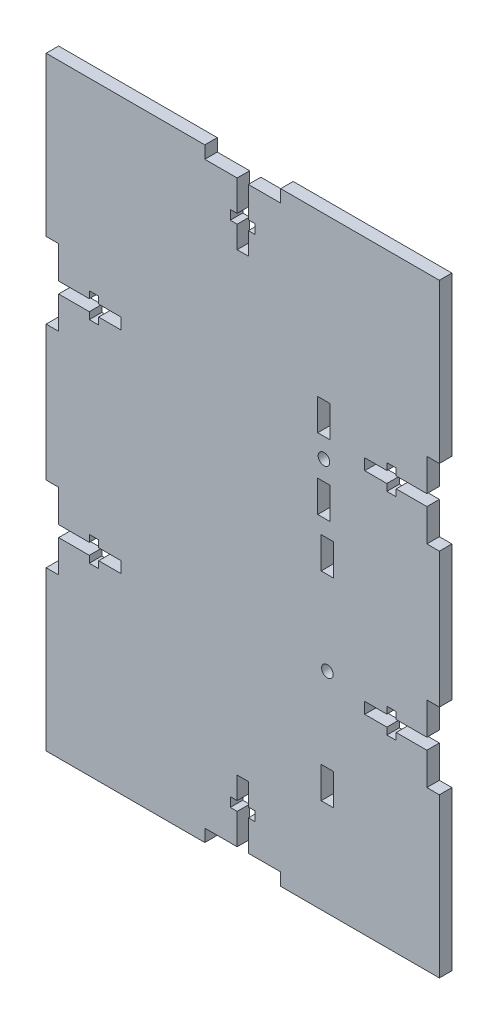
SolidWorks part; units mm, degrees
ref_plane "Front Plane" through (0, 0, 0) normal (0, 0, 1) x (1, 0, 0)
ref_plane "Top Plane" through (0, 0, 0) normal (0, 1, 0) x (1, 0, 0)
ref_plane "Right Plane" through (0, 0, 0) normal (1, 0, 0) x (0, 0, -1)
sketch "Sketch1" plane through (0, 0, 0) normal (0, 0, 1) x (1, 0, 0)
  line L0 (-50, 76.825) -> (-16.6667, 76.825)
  line L1 (-50, -76.825) -> (50, -76.825)
  line L2 (-50, -76.825) -> (-50, 76.825)
  line L3 (-50, 76.825) -> (50, 76.825) construction
  line L4 (50, -76.825) -> (50, 76.825)
  line L5 (-50, -76.825) -> (50, 76.825) construction
  line L6 (-50, 76.825) -> (50, -76.825) construction
  line L7 (-16.6667, 76.825) -> (16.6667, 76.825)
  line L8 (16.6667, 76.825) -> (50, 76.825)
  point P0 (0, 0)
  dimension "D1" = 100
  dimension "D2" = 153.65
extrude "Boss-Extrude1" add sketch "Sketch1" along normal blind 3.18
sketch "Sketch3" [suppressed] plane through (0, 0, 0) normal (0, 0, -1) x (-1, 0, 0)
  line L0 (-32.675, 34.075) -> (-32.675, -61.675)
  line L1 (-32.675, -61.675) -> (32.675, -61.675)
  line L2 (32.675, -61.675) -> (32.675, 34.075)
  line L3 (32.675, 34.075) -> (9.5, 34.075)
  line L4 (9.5, 34.075) -> (9.5, 37.075)
  line L5 (9.5, 37.075) -> (-9.5, 37.075)
  line L6 (-9.5, 37.075) -> (-9.5, 34.075)
  line L7 (-9.5, 34.075) -> (-32.675, 34.075)
  line L8 (32.675, 44.075) -> (-32.675, 44.075)
  line L9 (32.675, -61.675) -> (32.675, 44.075)
  line L10 (-32.675, -61.675) -> (32.675, -61.675)
  line L11 (-32.675, 44.075) -> (-32.675, -61.675)
  line L12 (-32.675, -61.675) -> (-32.675, -73.645) construction
  line L13 (44.645, -73.645) -> (-44.645, -73.645) construction
  line L14 (-32.675, -61.675) -> (-44.645, -61.675) construction
  line L15 (-44.645, -73.645) -> (-44.645, 73.645) construction
  line L16 (32.675, -61.675) -> (44.645, -61.675) construction
  line L17 (44.645, 73.645) -> (44.645, -73.645) construction
  dimension "D1" = 65.35
  dimension "D2" = 95.75
  dimension "D3" = 105.75
  dimension "D4" = 19
  dimension "D5" = 3
extrude "Cut-Extrude1" [suppressed] cut sketch "Sketch3" against normal through all contours L6 L7 L0 L1 L2 L3 L4 L5
sketch "Sketch9" [suppressed] plane through (-44.645, 0, 0) normal (-1, 0, 0) x (0, 0, 1)
  line L0 (0, 0) -> (3.18, 0) construction
  line L1 (0, 50) -> (0, -50) construction
  line L2 (3.18, 50) -> (3.18, -50) construction
  line L4 (0, -9.65) -> (3.18, -9.65)
  line L5 (0, -9.65) -> (0, 9.65)
  line L6 (0, 9.65) -> (3.18, 9.65)
  line L7 (3.18, -9.65) -> (3.18, 9.65)
  line L8 (0, -9.65) -> (3.18, 9.65) construction
  line L9 (0, 9.65) -> (3.18, -9.65) construction
  point P6 (1.59, 0)
  dimension "D1" = 19.3
extrude "Boss-Extrude4" [suppressed] add sketch "Sketch9" along normal blind 3.18
sketch "Sketch10" [suppressed] plane through (0, 0, 3.18) normal (0, 0, 1) x (1, 0, 0)
  line L0 (-46.235, 9.65) -> (-46.235, -9.65) construction
  line L1 (-47.825, 9.65) -> (-44.645, 9.65) construction
  line L2 (-47.825, -9.65) -> (-44.645, -9.65) construction
  circle A0 centre (-46.235, 0) radius 1.425
extrude "Cut-Extrude4" [suppressed] cut sketch "Sketch10" against normal through all
mirror "Mirror1" [suppressed] about plane through (0, 0, 0) normal (1, 0, 0)
sketch "Sketch18" [suppressed] plane through (44.645, 0, 0) normal (1, 0, 0) x (0, 0, -1)
  line L0 (0, 0) -> (-3.18, 0) construction
  line L1 (0, -50) -> (0, 50) construction
  line L2 (-3.18, -50) -> (-3.18, 50) construction
  line L4 (-3.18, -9.65) -> (0, -9.65)
  line L5 (-3.18, -9.65) -> (-3.18, 9.65)
  line L6 (-3.18, 9.65) -> (0, 9.65)
  line L7 (0, -9.65) -> (0, 9.65)
  line L8 (-3.18, -9.65) -> (0, 9.65) construction
  line L9 (-3.18, 9.65) -> (0, -9.65) construction
  point P6 (-1.59, 0)
  dimension "D1" = 19.3
extrude "Boss-Extrude8" [suppressed] add sketch "Sketch18" along normal blind 3.18
sketch "Sketch19" [suppressed] plane through (0, 0, 3.18) normal (0, 0, 1) x (1, 0, 0)
  line L0 (46.235, -9.65) -> (46.235, 9.65) construction
  line L1 (47.825, -9.65) -> (44.645, -9.65) construction
  line L2 (47.825, 9.65) -> (44.645, 9.65) construction
  circle A0 centre (46.235, 0) radius 1.425
extrude "Cut-Extrude8" [suppressed] cut sketch "Sketch19" against normal through all
mirror "Mirror2" [suppressed] about plane through (0, 0, 0) normal (1, 0, 0)
sketch "Sketch20" plane through (0, 0, 3.18) normal (0, 0, 1) x (1, 0, 0)
  line L0 (0, 70.465) -> (0, 0) construction
  line L1 (50, 76.825) -> (-50, 76.825) construction
  line L2 (-9.65, 76.825) -> (9.65, 76.825)
  line L3 (9.65, 76.825) -> (9.65, 73.645)
  line L4 (9.65, 73.645) -> (1.425, 73.645)
  line L5 (1.425, 73.645) -> (1.425, 65.845)
  line L6 (1.425, 65.845) -> (3.175, 65.845)
  line L7 (3.175, 65.845) -> (3.175, 63.465)
  line L8 (3.175, 63.465) -> (1.425, 63.465)
  line L9 (1.425, 63.465) -> (1.425, 57.845)
  line L10 (1.425, 57.845) -> (-1.425, 57.845)
  line L11 (-1.425, 57.845) -> (-1.425, 63.465)
  line L12 (-1.425, 63.465) -> (-3.175, 63.465)
  line L13 (-3.175, 63.465) -> (-3.175, 65.845)
  line L14 (-3.175, 65.845) -> (-1.425, 65.845)
  line L15 (-1.425, 65.845) -> (-1.425, 73.645)
  line L16 (-1.425, 73.645) -> (-9.65, 73.645)
  line L17 (-9.65, 73.645) -> (-9.65, 76.825)
  dimension "D1" = 19.3
  dimension "D2" = 3.18
  dimension "D3" = 15.8
  dimension "D4" = 6.35
  dimension "D5" = 2.38
  dimension "D6" = 2.85
  dimension "D7" = 7.8
extrude "Cut-Extrude9" cut sketch "Sketch20" against normal through all
mirror "Mirror3" about plane through (0, 0, 0) normal (0, 1, 0) of "Cut-Extrude9"
sketch "Sketch23" plane through (0, 0, 3.18) normal (0, 0, 1) x (1, 0, 0)
  line L0 (-50, 17.175) -> (-50, 36.475)
  line L1 (-50, 76.825) -> (-50, -76.825) construction
  line L2 (-50, 36.475) -> (-46.82, 36.475)
  line L3 (-46.82, 36.475) -> (-46.82, 28.25)
  line L4 (-46.82, 28.25) -> (-39.02, 28.25)
  line L5 (-39.02, 28.25) -> (-39.02, 30)
  line L6 (-39.02, 30) -> (-36.64, 30)
  line L7 (-36.64, 30) -> (-36.64, 28.25)
  line L8 (-36.64, 28.25) -> (-31.02, 28.25)
  line L9 (-31.02, 28.25) -> (-31.02, 25.4)
  line L10 (-31.02, 25.4) -> (-36.64, 25.4)
  line L11 (-36.64, 25.4) -> (-36.64, 23.65)
  line L12 (-36.64, 23.65) -> (-39.02, 23.65)
  line L13 (-39.02, 23.65) -> (-39.02, 25.4)
  line L14 (-39.02, 25.4) -> (-46.82, 25.4)
  line L15 (-46.82, 25.4) -> (-46.82, 17.175)
  line L16 (-46.82, 17.175) -> (-50, 17.175)
  line L17 (-9.65, 76.825) -> (-50, 76.825) construction
  line L19 (-31.02, 26.825) -> (-50, 26.825) construction
  line L20 (-50, -36.475) -> (-50, -17.175)
  line L21 (-50, -17.175) -> (-46.82, -17.175)
  line L22 (-46.82, -17.175) -> (-46.82, -25.4)
  line L23 (-46.82, -25.4) -> (-39.02, -25.4)
  line L24 (-39.02, -25.4) -> (-39.02, -23.65)
  line L25 (-39.02, -23.65) -> (-36.64, -23.65)
  line L26 (-36.64, -23.65) -> (-36.64, -25.4)
  line L27 (-36.64, -25.4) -> (-31.02, -25.4)
  line L28 (-31.02, -25.4) -> (-31.02, -28.25)
  line L29 (-31.02, -28.25) -> (-36.64, -28.25)
  line L30 (-36.64, -28.25) -> (-36.64, -30)
  line L31 (-36.64, -30) -> (-39.02, -30)
  line L32 (-39.02, -30) -> (-39.02, -28.25)
  line L33 (-39.02, -28.25) -> (-46.82, -28.25)
  line L34 (-46.82, -28.25) -> (-46.82, -36.475)
  line L35 (-46.82, -36.475) -> (-50, -36.475)
  line L36 (-50, -26.825) -> (-31.02, -26.825) construction
  line L37 (-50, -76.825) -> (-9.65, -76.825) construction
  dimension "D1" = 50
  dimension "D2" = 19.3
  dimension "D3" = 3.18
  dimension "D4" = 15.8
  dimension "D5" = 6.35
  dimension "D6" = 2.85
  dimension "D7" = 7.8
  dimension "D8" = 2.38
  dimension "D9" = 19.3
  dimension "D10" = 3.18
  dimension "D11" = 7.8
  dimension "D12" = 15.8
  dimension "D13" = 6.35
  dimension "D14" = 2.85
  dimension "D15" = 2.38
  dimension "D16" = 50
  dimension "D17" = 1.75
extrude "Cut-Extrude10" cut sketch "Sketch23" against normal through all
sketch "Sketch24" [suppressed] plane through (0, 0, 3.18) normal (0, 0, 1) x (1, 0, 0)
  line L0 (50, -17.175) -> (50, -36.475)
  line L1 (50, -76.825) -> (50, 76.825) construction
  line L2 (50, -36.475) -> (46.82, -36.475)
  line L3 (46.82, -36.475) -> (46.82, -28.25)
  line L4 (46.82, -28.25) -> (39.02, -28.25)
  line L5 (39.02, -28.25) -> (39.02, -30)
  line L6 (39.02, -30) -> (36.64, -30)
  line L7 (36.64, -30) -> (36.64, -28.25)
  line L8 (36.64, -28.25) -> (31.02, -28.25)
  line L9 (31.02, -28.25) -> (31.02, -25.4)
  line L10 (31.02, -25.4) -> (36.64, -25.4)
  line L11 (36.64, -25.4) -> (36.64, -23.65)
  line L12 (36.64, -23.65) -> (39.02, -23.65)
  line L13 (39.02, -23.65) -> (39.02, -25.4)
  line L14 (39.02, -25.4) -> (46.82, -25.4)
  line L15 (46.82, -25.4) -> (46.82, -17.175)
  line L16 (46.82, -17.175) -> (50, -17.175)
  line L17 (31.02, -26.825) -> (50, -26.825) construction
  line L18 (9.65, -76.825) -> (50, -76.825) construction
  line L19 (50, 36.475) -> (50, 17.175)
  line L20 (50, 17.175) -> (46.82, 17.175)
  line L21 (46.82, 17.175) -> (46.82, 25.4)
  line L22 (46.82, 25.4) -> (39.02, 25.4)
  line L23 (39.02, 25.4) -> (39.02, 23.65)
  line L24 (39.02, 23.65) -> (36.64, 23.65)
  line L25 (36.64, 23.65) -> (36.64, 25.4)
  line L26 (36.64, 25.4) -> (31.02, 25.4)
  line L27 (31.02, 25.4) -> (31.02, 28.25)
  line L28 (31.02, 28.25) -> (36.64, 28.25)
  line L29 (36.64, 28.25) -> (36.64, 30)
  line L30 (36.64, 30) -> (39.02, 30)
  line L31 (39.02, 30) -> (39.02, 28.25)
  line L32 (39.02, 28.25) -> (46.82, 28.25)
  line L33 (46.82, 28.25) -> (46.82, 36.475)
  line L34 (46.82, 36.475) -> (50, 36.475)
  line L35 (31.02, 26.825) -> (50, 26.825) construction
  line L36 (50, 76.825) -> (9.65, 76.825) construction
  dimension "D1" = 19.3
  dimension "D2" = 3.18
  dimension "D3" = 15.8
  dimension "D4" = 7.8
  dimension "D5" = 6.35
  dimension "D6" = 2.85
  dimension "D7" = 2.38
  dimension "D8" = 50
  dimension "D9" = 19.3
  dimension "D10" = 3.18
  dimension "D11" = 7.8
  dimension "D12" = 15.8
  dimension "D13" = 6.35
  dimension "D14" = 2.85
  dimension "D15" = 2.38
  dimension "D16" = 50
extrude "Cut-Extrude11" [suppressed] cut sketch "Sketch24" against normal through all
sketch "Sketch25" [suppressed] plane through (0, 0, 3.18) normal (0, 0, 1) x (1, 0, 0)
  line L0 (9.65, -50) -> (-9.65, -50)
  line L1 (-44.645, -50) -> (44.645, -50) construction
  line L2 (-9.65, -50) -> (-9.65, -46.82)
  line L3 (-9.65, -46.82) -> (-1.425, -46.82)
  line L4 (-1.425, -46.82) -> (-1.425, -39.02)
  line L5 (-1.425, -39.02) -> (-3.175, -39.02)
  line L6 (-3.175, -39.02) -> (-3.175, -36.64)
  line L7 (-3.175, -36.64) -> (-1.425, -36.64)
  line L8 (-1.425, -36.64) -> (-1.425, -31.02)
  line L9 (-1.425, -31.02) -> (1.425, -31.02)
  line L10 (1.425, -31.02) -> (1.425, -36.64)
  line L11 (1.425, -36.64) -> (3.175, -36.64)
  line L12 (3.175, -36.64) -> (3.175, -39.02)
  line L13 (3.175, -39.02) -> (1.425, -39.02)
  line L14 (1.425, -39.02) -> (1.425, -46.82)
  line L15 (1.425, -46.82) -> (9.65, -46.82)
  line L16 (9.65, -46.82) -> (9.65, -50)
  line L17 (0, -50) -> (0, 0) construction
  dimension "D1" = 19.3
  dimension "D2" = 3.18
  dimension "D3" = 15.8
  dimension "D4" = 7.8
  dimension "D5" = 6.35
  dimension "D6" = 2.85
  dimension "D7" = 2.38
extrude "Cut-Extrude12" [suppressed] cut sketch "Sketch25" against normal through all
sketch "Sketch26" [suppressed] plane through (0, 0, 3.18) normal (0, 0, 1) x (1, 0, 0)
  line L0 (-9.65, 50) -> (9.65, 50)
  line L1 (44.645, 50) -> (-44.645, 50) construction
  line L2 (9.65, 50) -> (9.65, 46.82)
  line L3 (9.65, 46.82) -> (1.425, 46.82)
  line L4 (1.425, 46.82) -> (1.425, 39.02)
  line L5 (1.425, 39.02) -> (3.175, 39.02)
  line L6 (3.175, 39.02) -> (3.175, 36.64)
  line L7 (3.175, 36.64) -> (1.425, 36.64)
  line L8 (1.425, 36.64) -> (1.425, 31.02)
  line L9 (1.425, 31.02) -> (-1.425, 31.02)
  line L10 (-1.425, 31.02) -> (-1.425, 36.64)
  line L11 (-1.425, 36.64) -> (-3.175, 36.64)
  line L12 (-3.175, 36.64) -> (-3.175, 39.02)
  line L13 (-3.175, 39.02) -> (-1.425, 39.02)
  line L14 (-1.425, 39.02) -> (-1.425, 46.82)
  line L15 (-1.425, 46.82) -> (-9.65, 46.82)
  line L16 (-9.65, 46.82) -> (-9.65, 50)
  line L17 (0, 50) -> (0, -4.4192) construction
  dimension "D1" = 19.3
  dimension "D2" = 3.18
  dimension "D3" = 7.8
  dimension "D4" = 15.8
  dimension "D5" = 6.35
  dimension "D6" = 2.85
  dimension "D7" = 2.38
extrude "Cut-Extrude13" [suppressed] cut sketch "Sketch26" against normal through all
mirror "Mirror4" about plane through (0, 0, 0) normal (1, 0, 0) of "Cut-Extrude10"
mirror "Mirror5" [suppressed] about plane through (0, 0, 0) normal (1, 0, 0)
mirror "Mirror6" [suppressed] about plane through (0, 0, 0) normal (0, 1, 0)
mirror "Mirror7" [suppressed] about plane through (0, 0, 0) normal (0, 1, 0)
sketch "Sketch27" [suppressed] plane through (-44.645, 0, 0) normal (-1, 0, 0) x (0, 0, 1)
  line L0 (0, -36.475) -> (0, -17.175)
  line L1 (0, 73.645) -> (0, -73.645) construction
  line L2 (0, -17.175) -> (3.18, -17.175)
  line L3 (3.18, 73.645) -> (3.18, -73.645) construction
  line L4 (3.18, -17.175) -> (3.18, -36.475)
  line L5 (3.18, -36.475) -> (0, -36.475)
  line L6 (3.18, -26.825) -> (0, -26.825) construction
  line L7 (3.18, -73.645) -> (0, -73.645) construction
  dimension "D1" = 19.3
  dimension "D2" = 46.82
extrude "Boss-Extrude9" [suppressed] add sketch "Sketch27" along normal blind 3.18
sketch "Sketch28" [suppressed] plane through (0, -73.645, 0) normal (0, -1, 0) x (1, 0, 0)
  line L0 (9.65, 0) -> (-9.65, 0)
  line L1 (-44.645, 0) -> (44.645, 0) construction
  line L2 (-9.65, 0) -> (-9.65, 3.18)
  line L3 (-44.645, 3.18) -> (44.645, 3.18) construction
  line L4 (-9.65, 3.18) -> (9.65, 3.18)
  line L5 (9.65, 3.18) -> (9.65, 0)
  line L6 (0, 0) -> (0, 3.18) construction
  dimension "D1" = 19.3
extrude "Boss-Extrude10" [suppressed] add sketch "Sketch28" along normal blind 3.18
sketch "Sketch29" [suppressed] plane through (0, 0, 3.18) normal (0, 0, 1) x (1, 0, 0)
  line L0 (-47.825, -26.825) -> (-37.3062, -26.825) construction
  line L1 (-47.825, -36.475) -> (-47.825, -17.175) construction
  line L2 (-46.235, -17.175) -> (-46.235, -36.475) construction
  line L3 (-47.825, -17.175) -> (-44.645, -17.175) construction
  line L4 (-47.825, -36.475) -> (-44.645, -36.475) construction
  circle A0 centre (-46.235, -26.825) radius 1.425
extrude "Cut-Extrude14" [suppressed] cut sketch "Sketch29" against normal through all
sketch "Sketch30" [suppressed] plane through (0, 0, 3.18) normal (0, 0, 1) x (1, 0, 0)
  line L0 (0, -76.825) -> (0, -66.2855) construction
  line L1 (9.65, -76.825) -> (-9.65, -76.825) construction
  line L2 (9.65, -75.235) -> (-9.65, -75.235) construction
  line L3 (9.65, -76.825) -> (9.65, -73.645) construction
  line L4 (-9.65, -76.825) -> (-9.65, -73.645) construction
  circle A0 centre (0, -75.235) radius 1.425
extrude "Cut-Extrude15" [suppressed] cut sketch "Sketch30" against normal through all
mirror "Mirror8" [suppressed] about plane through (0, 0, 0) normal (1, 0, 0)
mirror "Mirror9" [suppressed] about plane through (0, 0, 0) normal (0, 1, 0)
sketch "Sketch31" [suppressed] plane through (0, 0, 3.18) normal (0, 0, 1) x (1, 0, 0)
  line L0 (14.341, -8.1358) -> (14.341, -12.6358) construction
  line L8 (5.175, -1.9558) -> (5.175, 19.3642) construction
  line L10 (-24.825, 19.3642) -> (-24.825, -1.9558) construction
  line L11 (5.175, 19.3642) -> (-24.825, 19.3642) construction
  line L16 (23.507, -9.6358) -> (39.341, -9.6358) construction
  line L17 (23.507, 19.3642) -> (23.507, -9.6358) construction
  line L18 (39.341, 19.3642) -> (23.507, 19.3642) construction
  line L19 (39.341, -9.6358) -> (39.341, 19.3642) construction
  line L26 (14.341, -15.8158) -> (14.341, -12.6358) construction
  line L29 (-24.825, -1.9558) -> (5.175, -1.9558) construction
  line L34 (20.5772, -7.1358) -> (20.5772, 11.3642) construction
  line L35 (20.5772, 11.3642) -> (8.1048, 11.3642) construction
  line L36 (8.1048, 11.3642) -> (8.1048, -7.1358) construction
  line L37 (9.7431, -8.1358) -> (18.9389, -8.1358) construction
  line L38 (14.341, -15.8158) -> (14.341, -50) construction
  line L39 (-17.325, 9.65) -> (-24.825, 9.65) construction
  line L40 (-6.159, -12.4758) -> (34.841, -12.4758)
  line L41 (-6.159, -12.4758) -> (-6.159, -15.9758)
  line L42 (-6.159, -15.9758) -> (34.841, -15.9758)
  line L43 (34.841, -12.4758) -> (34.841, -15.9758)
  line L88 (-44.645, -50) -> (-9.65, -50) construction
  line L89 (-9.65, -50) -> (-9.65, -46.82) construction
  line L90 (-9.65, -46.82) -> (-1.425, -46.82) construction
  line L91 (-1.425, -46.82) -> (-1.425, -39.02) construction
  line L92 (-1.425, -39.02) -> (-3.175, -39.02) construction
  line L93 (-3.175, -39.02) -> (-3.175, -36.64) construction
  line L94 (-3.175, -36.64) -> (-1.425, -36.64) construction
  line L95 (-1.425, -36.64) -> (-1.425, -31.02) construction
  line L96 (-1.425, -31.02) -> (1.425, -31.02) construction
  line L97 (1.425, -31.02) -> (1.425, -36.64) construction
  line L98 (1.425, -36.64) -> (3.175, -36.64) construction
  line L99 (3.175, -36.64) -> (3.175, -39.02) construction
  line L100 (3.175, -39.02) -> (1.425, -39.02) construction
  line L101 (1.425, -39.02) -> (1.425, -46.82) construction
  line L102 (1.425, -46.82) -> (9.65, -46.82) construction
  line L103 (9.65, -46.82) -> (9.65, -50) construction
  line L104 (9.65, -50) -> (44.645, -50) construction
  line L105 (44.645, -50) -> (44.645, -9.65) construction
  line L106 (44.645, -9.65) -> (47.825, -9.65) construction
  line L107 (47.825, -9.65) -> (47.825, 9.65) construction
  line L108 (47.825, 9.65) -> (44.645, 9.65) construction
  line L109 (44.645, 9.65) -> (44.645, 50) construction
  line L110 (44.645, 50) -> (9.65, 50) construction
  line L111 (9.65, 50) -> (9.65, 46.82) construction
  line L112 (9.65, 46.82) -> (1.425, 46.82) construction
  line L113 (1.425, 46.82) -> (1.425, 39.02) construction
  line L114 (1.425, 39.02) -> (3.175, 39.02) construction
  line L115 (3.175, 39.02) -> (3.175, 36.64) construction
  line L116 (3.175, 36.64) -> (1.425, 36.64) construction
  line L117 (1.425, 36.64) -> (1.425, 31.02) construction
  line L118 (1.425, 31.02) -> (-1.425, 31.02) construction
  line L119 (-1.425, 31.02) -> (-1.425, 36.64) construction
  line L120 (-1.425, 36.64) -> (-3.175, 36.64) construction
  line L121 (-3.175, 36.64) -> (-3.175, 39.02) construction
  line L122 (-3.175, 39.02) -> (-1.425, 39.02) construction
  line L123 (-1.425, 39.02) -> (-1.425, 46.82) construction
  line L124 (-1.425, 46.82) -> (-9.65, 46.82) construction
  line L125 (-9.65, 46.82) -> (-9.65, 50) construction
  line L126 (-9.65, 50) -> (-44.645, 50) construction
  line L127 (-44.645, 50) -> (-44.645, 9.65) construction
  line L128 (-44.645, 9.65) -> (-47.825, 9.65) construction
  line L129 (-47.825, 9.65) -> (-47.825, -9.65) construction
  line L130 (-47.825, -9.65) -> (-44.645, -9.65) construction
  line L131 (-44.645, -9.65) -> (-44.645, -50) construction
  line L132 (-6.159, -12.4758) -> (34.841, -15.9758) construction
  line L133 (-6.159, -15.9758) -> (34.841, -12.4758) construction
  line L134 (-17.325, 9.65) -> (-17.325, -1.9558) construction
  line L135 (31.3061, 4.8642) -> (39.341, 4.8642) construction
  line L136 (31.3061, 4.8642) -> (31.3061, 19.3642) construction
  line L137 (-17.325, 9.65) -> (-4.325, 9.65) construction
  circle A0 centre (-17.325, 9.65) radius 1.5
  circle A1 centre (31.3061, 4.8642) radius 1.5
  circle A2 centre (-4.325, 9.65) radius 1.5
  spline S4 degree 3 poles (8.1048, -7.1358) (8.1048, -7.3148) (8.1799, -7.485) (8.4092, -7.7556) (8.5582, -7.8571) (8.8762, -8.0081) (9.0479, -8.0586) (9.3919, -8.1221) (9.5665, -8.1358) (9.7431, -8.1358) knots 0 0 0 0 0.25 0.25 0.5 0.5 0.75 0.75 1 1 1 1 construction
  spline S5 degree 3 poles (18.9389, -8.1358) (19.1156, -8.1358) (19.2906, -8.1221) (19.6363, -8.0581) (19.8071, -8.0076) (20.1239, -7.857) (20.2729, -7.7556) (20.5025, -7.4843) (20.5772, -7.3148) (20.5772, -7.1358) knots 0 0 0 0 0.25 0.25 0.5 0.5 0.75 0.75 1 1 1 1 construction
  point P14 (14.341, -14.2258)
  point P46 (-44.645, 50)
  dimension "D6" = 3
  dimension "D4" = 41
  dimension "D5" = 3.5
  dimension "D7" = 7.5
  dimension "D9" = 13
extrude "Cut-Extrude16" [suppressed] cut sketch "Sketch31" against normal through all contours L41 L40 L43 L42 | A1 | A2 | A0
sketch "Sketch32" plane through (0, 0, 3.18) normal (0, 0, 1) x (1, 0, 0)
  line L0 (22.24, 17.7829) -> (22.24, 9.7829)
  line L1 (22.24, 35.7829) -> (22.24, 27.7829)
  line L2 (22.24, 35.7829) -> (19.06, 35.7829)
  line L3 (22.24, 35.7829) -> (22.24, 27.7829)
  line L4 (22.24, 27.7829) -> (19.06, 27.7829)
  line L5 (19.06, 35.7829) -> (19.06, 27.7829)
  line L6 (22.24, 17.7829) -> (19.06, 17.7829)
  line L7 (22.24, 17.7829) -> (22.24, 9.7829)
  line L8 (22.24, 9.7829) -> (19.06, 9.7829)
  line L9 (19.06, 17.7829) -> (19.06, 9.7829)
  line L10 (22.24, 17.7829) -> (22.24, 27.7829) construction
  line L11 (50, -17.175) -> (50, 17.175) construction
  line L12 (50, 17.175) -> (46.82, 17.175) construction
  line L13 (46.82, 17.175) -> (46.82, 25.4) construction
  line L14 (46.82, 25.4) -> (39.02, 25.4) construction
  line L15 (39.02, 25.4) -> (39.02, 23.65) construction
  line L16 (39.02, 23.65) -> (36.64, 23.65) construction
  line L17 (36.64, 23.65) -> (36.64, 25.4) construction
  line L18 (36.64, 25.4) -> (31.02, 25.4) construction
  line L19 (31.02, 25.4) -> (31.02, 28.25) construction
  line L20 (31.02, 28.25) -> (36.64, 28.25) construction
  line L21 (36.64, 28.25) -> (36.64, 30) construction
  line L22 (36.64, 30) -> (39.02, 30) construction
  line L23 (39.02, 30) -> (39.02, 28.25) construction
  line L24 (39.02, 28.25) -> (46.82, 28.25) construction
  line L25 (46.82, 28.25) -> (46.82, 36.475) construction
  line L26 (46.82, 36.475) -> (50, 36.475) construction
  line L27 (50, 36.475) -> (50, 76.825) construction
  line L28 (50, 76.825) -> (9.65, 76.825) construction
  line L29 (9.65, 76.825) -> (9.65, 73.645) construction
  line L30 (9.65, 73.645) -> (1.425, 73.645) construction
  line L31 (1.425, 73.645) -> (1.425, 65.845) construction
  line L32 (1.425, 65.845) -> (3.175, 65.845) construction
  line L33 (3.175, 65.845) -> (3.175, 63.465) construction
  line L34 (3.175, 63.465) -> (1.425, 63.465) construction
  line L35 (1.425, 63.465) -> (1.425, 57.845) construction
  line L36 (1.425, 57.845) -> (-1.425, 57.845) construction
  line L37 (-1.425, 57.845) -> (-1.425, 63.465) construction
  line L38 (-1.425, 63.465) -> (-3.175, 63.465) construction
  line L39 (-3.175, 63.465) -> (-3.175, 65.845) construction
  line L40 (-3.175, 65.845) -> (-1.425, 65.845) construction
  line L41 (-1.425, 65.845) -> (-1.425, 73.645) construction
  line L42 (-1.425, 73.645) -> (-9.65, 73.645) construction
  line L43 (-9.65, 73.645) -> (-9.65, 76.825) construction
  line L44 (-9.65, 76.825) -> (-50, 76.825) construction
  line L45 (-50, 76.825) -> (-50, 36.475) construction
  line L46 (-50, 36.475) -> (-46.82, 36.475) construction
  line L47 (-46.82, 36.475) -> (-46.82, 28.25) construction
  line L48 (-46.82, 28.25) -> (-39.02, 28.25) construction
  line L49 (-39.02, 28.25) -> (-39.02, 30) construction
  line L50 (-39.02, 30) -> (-36.64, 30) construction
  line L51 (-36.64, 30) -> (-36.64, 28.25) construction
  line L52 (-36.64, 28.25) -> (-31.02, 28.25) construction
  line L53 (-31.02, 28.25) -> (-31.02, 25.4) construction
  line L54 (-31.02, 25.4) -> (-36.64, 25.4) construction
  line L55 (-36.64, 25.4) -> (-36.64, 23.65) construction
  line L56 (-36.64, 23.65) -> (-39.02, 23.65) construction
  line L57 (-39.02, 23.65) -> (-39.02, 25.4) construction
  line L58 (-39.02, 25.4) -> (-46.82, 25.4) construction
  line L59 (-46.82, 25.4) -> (-46.82, 17.175) construction
  line L60 (-46.82, 17.175) -> (-50, 17.175) construction
  line L61 (-50, 17.175) -> (-50, -17.175) construction
  line L62 (-50, -17.175) -> (-46.82, -17.175) construction
  line L63 (-46.82, -17.175) -> (-46.82, -25.4) construction
  line L64 (-46.82, -25.4) -> (-39.02, -25.4) construction
  line L65 (-39.02, -25.4) -> (-39.02, -23.65) construction
  line L66 (-39.02, -23.65) -> (-36.64, -23.65) construction
  line L67 (-36.64, -23.65) -> (-36.64, -25.4) construction
  line L68 (-36.64, -25.4) -> (-31.02, -25.4) construction
  line L69 (-31.02, -25.4) -> (-31.02, -28.25) construction
  line L70 (-31.02, -28.25) -> (-36.64, -28.25) construction
  line L71 (-36.64, -28.25) -> (-36.64, -30) construction
  line L72 (-36.64, -30) -> (-39.02, -30) construction
  line L73 (-39.02, -30) -> (-39.02, -28.25) construction
  line L74 (-39.02, -28.25) -> (-46.82, -28.25) construction
  line L75 (-46.82, -28.25) -> (-46.82, -36.475) construction
  line L76 (-46.82, -36.475) -> (-50, -36.475) construction
  line L77 (-50, -36.475) -> (-50, -76.825) construction
  line L78 (-50, -76.825) -> (-9.65, -76.825) construction
  line L79 (-9.65, -76.825) -> (-9.65, -73.645) construction
  line L80 (-9.65, -73.645) -> (-1.425, -73.645) construction
  line L81 (-1.425, -73.645) -> (-1.425, -65.845) construction
  line L82 (-1.425, -65.845) -> (-3.175, -65.845) construction
  line L83 (-3.175, -65.845) -> (-3.175, -63.465) construction
  line L84 (-3.175, -63.465) -> (-1.425, -63.465) construction
  line L85 (-1.425, -63.465) -> (-1.425, -57.845) construction
  line L86 (-1.425, -57.845) -> (1.425, -57.845) construction
  line L87 (1.425, -57.845) -> (1.425, -63.465) construction
  line L88 (1.425, -63.465) -> (3.175, -63.465) construction
  line L89 (3.175, -63.465) -> (3.175, -65.845) construction
  line L90 (3.175, -65.845) -> (1.425, -65.845) construction
  line L91 (1.425, -65.845) -> (1.425, -73.645) construction
  line L92 (1.425, -73.645) -> (9.65, -73.645) construction
  line L93 (9.65, -73.645) -> (9.65, -76.825) construction
  line L94 (9.65, -76.825) -> (50, -76.825) construction
  line L95 (50, -76.825) -> (50, -36.475) construction
  line L96 (50, -36.475) -> (46.82, -36.475) construction
  line L97 (46.82, -36.475) -> (46.82, -28.25) construction
  line L98 (46.82, -28.25) -> (39.02, -28.25) construction
  line L99 (39.02, -28.25) -> (39.02, -30) construction
  line L100 (39.02, -30) -> (36.64, -30) construction
  line L101 (36.64, -30) -> (36.64, -28.25) construction
  line L102 (36.64, -28.25) -> (31.02, -28.25) construction
  line L103 (31.02, -28.25) -> (31.02, -25.4) construction
  line L104 (31.02, -25.4) -> (36.64, -25.4) construction
  line L105 (36.64, -25.4) -> (36.64, -23.65) construction
  line L106 (36.64, -23.65) -> (39.02, -23.65) construction
  line L107 (39.02, -23.65) -> (39.02, -25.4) construction
  line L108 (39.02, -25.4) -> (46.82, -25.4) construction
  line L109 (46.82, -25.4) -> (46.82, -17.175) construction
  line L110 (46.82, -17.175) -> (50, -17.175) construction
  line L111 (20.65, 27.7829) -> (20.65, 17.7829) construction
  line L112 (0, 0) -> (0, 57.845) construction
  line L113 (-20.65, 27.7829) -> (-20.65, 17.7829) construction
  line L114 (-22.24, 17.7829) -> (-22.24, 27.7829) construction
  line L115 (-19.06, 17.7829) -> (-19.06, 9.7829)
  line L116 (-22.24, 9.7829) -> (-19.06, 9.7829)
  line L117 (-22.24, 17.7829) -> (-22.24, 9.7829)
  line L118 (-22.24, 17.7829) -> (-19.06, 17.7829)
  line L119 (-19.06, 35.7829) -> (-19.06, 27.7829)
  line L120 (-22.24, 27.7829) -> (-19.06, 27.7829)
  line L121 (-22.24, 35.7829) -> (-22.24, 27.7829)
  line L122 (-22.24, 35.7829) -> (-19.06, 35.7829)
  line L123 (-22.24, 35.7829) -> (-22.24, 27.7829)
  line L124 (-22.24, 17.7829) -> (-22.24, 9.7829)
  circle A0 centre (20.65, 22.7829) radius 1.47
  circle A1 centre (-20.65, 22.7829) radius 1.47
  dimension "D1" = 2.94
extrude "Cut-Extrude17" [suppressed] cut sketch "Sketch32" against normal through all contours L118 L117 L116 L115 | L122 L121 L120 L119 | A1
extrude "Cut-Extrude18" cut sketch "Sketch32<4>" against normal through all contours L2 L5 L4 L1 | A0 | L6 L9 L8 L0 region at (20.65, 13.7829, 3.18) region at (20.65, 31.7829, 3.18) region at (20.65, 22.7829, 3.18)
sketch "Sketch32<4>" plane through (0, 0, 3.18) normal (0, 0, 1) x (1, 0, 0) same geometry as "Sketch32"
sketch "Sketch33" plane through (0, 0, 0) normal (0, 0, 1) x (1, 0, 0)
  line L0 (0, -1.749) -> (0, 1.749) construction
  line L1 (19.94, 5.7884) -> (23.12, 5.7884)
  line L2 (19.94, -2.2116) -> (19.94, 5.7884)
  line L3 (23.12, -2.2116) -> (19.94, -2.2116)
  line L4 (23.12, 5.7884) -> (23.12, -2.2116)
  line L5 (19.94, -44.8116) -> (23.12, -44.8116)
  line L6 (19.94, -52.8116) -> (19.94, -44.8116)
  line L7 (23.12, -52.8116) -> (19.94, -52.8116)
  line L8 (23.12, -44.8116) -> (23.12, -52.8116)
  line L9 (-21.53, -2.2116) -> (-21.53, -44.8116) construction
  line L10 (21.53, -2.2116) -> (21.53, -44.8116) construction
  line L108 (-23.12, -44.8116) -> (-23.12, -52.8116)
  line L109 (-23.12, -52.8116) -> (-19.94, -52.8116)
  line L110 (-19.94, -52.8116) -> (-19.94, -44.8116)
  line L111 (-19.94, -44.8116) -> (-23.12, -44.8116)
  line L112 (-23.12, 5.7884) -> (-23.12, -2.2116)
  line L113 (-23.12, -2.2116) -> (-19.94, -2.2116)
  line L114 (-19.94, -2.2116) -> (-19.94, 5.7884)
  line L115 (-19.94, 5.7884) -> (-23.12, 5.7884)
  circle A0 centre (-21.53, -23.5116) radius 1.47
  circle A1 centre (21.53, -23.5116) radius 1.47
extrude "Cut-Extrude22" cut sketch "Sketch33" along normal through all contours L6 L5 L8 L7 | A1 | L4 L3 L2 L1
sketch "Sketch35" [suppressed] plane through (0, 0, 0) normal (0, 0, 1) x (-1, 0, 0)
  line L2 (17.677, 7.8541) -> (5.677, 7.8603)
  line L3 (17.6824, 18.354) -> (17.677, 7.8541)
  line L5 (5.6824, 18.3603) -> (17.6824, 18.354)
  line L7 (5.677, 7.8603) -> (5.6824, 18.3603)
extrude "Cut-Extrude26" [suppressed] cut sketch "Sketch35" along normal through all
sketch "Sketch36" [suppressed] plane through (0, 0, 3.18) normal (0, 0, 1) x (1, 0, 0)
  line L0 (-36.1816, -36.7568) -> (-21.1816, -36.7568) construction
  line L1 (-33.6816, -34.2568) -> (-23.6816, -34.2568)
  line L2 (-33.6816, -34.2568) -> (-33.6816, -39.2568)
  line L3 (-33.6816, -39.2568) -> (-23.6816, -39.2568)
  line L4 (-23.6816, -34.2568) -> (-23.6816, -39.2568)
  line L5 (-33.6816, -34.2568) -> (-23.6816, -39.2568) construction
  line L6 (-33.6816, -39.2568) -> (-23.6816, -34.2568) construction
  circle A0 centre (-21.1816, -36.7568) radius 1
  circle A1 centre (-36.1816, -36.7568) radius 1
  point P0 (-28.6816, -36.7568)
  point P8 (-28.6816, -36.7568)
  dimension "D4" = 2
  dimension "D1" = 10
  dimension "D2" = 5
  dimension "D3" = 15
extrude "Cut-Extrude27" [suppressed] cut sketch "Sketch36" against normal through all
